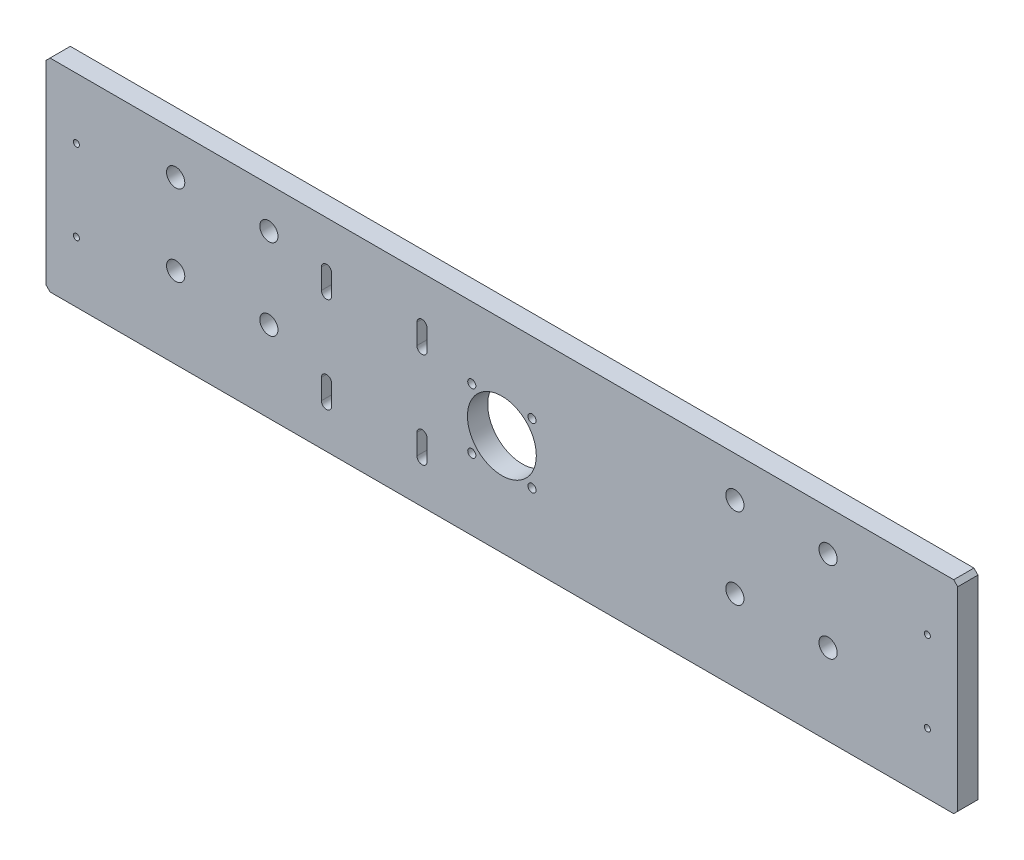
SolidWorks part; units mm, degrees
ref_plane "Piano frontale" through (0, 0, 0) normal (0, 0, 1) x (1, 0, 0)
ref_plane "Piano superiore" through (0, 0, 0) normal (0, 1, 0) x (1, 0, 0)
ref_plane "Piano destro" through (0, 0, 0) normal (1, 0, 0) x (0, 0, -1)
sketch "Schizzo1" plane through (0, 0, 0) normal (0, 0, 1) x (1, 0, 0)
  line L0 (225, 100) -> (225, 0) construction
  line L1 (2, 0) -> (448, 0)
  line L2 (0, 2) -> (0, 98)
  line L3 (2, 100) -> (448, 100)
  line L4 (450, 2) -> (450, 98)
  line L5 (87, 100) -> (87, 0) construction
  line L7 (225, 50) -> (243.5099, 50) construction
  line L9 (225, 50) -> (205.51, 69.49) construction
  line L21 (0, 98) -> (2, 100)
  line L22 (2, 0) -> (0, 2)
  line L23 (448, 0) -> (450, 2)
  line L24 (448, 100) -> (450, 98)
  circle A0 centre (225, 50) radius 17
  circle A1 centre (225, 50) radius 21 construction
  circle A2 centre (239.8492, 64.8492) radius 2
  circle A3 centre (239.8492, 35.1508) radius 2
  circle A4 centre (210.1508, 35.1508) radius 2
  circle A5 centre (386, 40) radius 4.5
  circle A6 centre (386, 80) radius 4.5
  circle A7 centre (340, 40) radius 4.5
  circle A8 centre (340, 80) radius 4.5
  circle A9 centre (435, 70) radius 1.5
  circle A10 centre (435, 30) radius 1.5
  circle A11 centre (15, 30) radius 1.5
  circle A13 centre (210.1508, 64.8492) radius 2
  circle A18 centre (15, 70) radius 1.5
  circle A29 centre (110, 80) radius 4.5
  circle A30 centre (110, 40) radius 4.5
  circle A32 centre (64, 80) radius 4.5
  circle A33 centre (64, 40) radius 4.5
  point P0 (0, 0)
  point P1 (450, 100)
  point P2 (0, 100)
  point P3 (450, 0)
  point P9 (210.1508, 64.8492)
  point P13 (210.1508, 64.8492)
  dimension "D4" = 34
  dimension "D10" = 23
  dimension "D15" = 3
  dimension "D17" = 4
  dimension "D8" = 45
  dimension "D5" = 42
  dimension "D9" = 64
  dimension "D11" = 9
  dimension "D1" = 100
  dimension "D2" = 450
  dimension "D6" = 20
  dimension "D7" = 40
  dimension "D14" = 30
  dimension "D16" = 15
extrude "Boss-Extrude1" add sketch "Schizzo1" against normal blind 10
sketch "Sketch1" plane through (0, 0, -10) normal (0, 0, -1) x (-1, 0, 0)
  line L0 (-185.5771, 72.6242) -> (-185.5771, 25.4842) construction
  line L1 (-138.4371, 72.6242) -> (-138.4371, 25.4842) construction
  line L2 (-185.5771, 67.6242) -> (-185.5771, 77.6242) construction
  line L3 (-188.0771, 67.6242) -> (-188.0771, 77.6242)
  line L4 (-183.0771, 67.6242) -> (-183.0771, 77.6242)
  line L5 (-185.5771, 49.0542) -> (-138.4371, 49.0542) construction
  line L6 (-162.0071, 49.0542) -> (-162.0071, 85.2274) construction
  line L7 (-138.4371, 67.6242) -> (-138.4371, 77.6242) construction
  line L8 (-140.9371, 67.6242) -> (-140.9371, 77.6242)
  line L9 (-135.9371, 67.6242) -> (-135.9371, 77.6242)
  line L10 (-185.5771, 20.4842) -> (-185.5771, 30.4842) construction
  line L11 (-188.0771, 20.4842) -> (-188.0771, 30.4842)
  line L12 (-183.0771, 20.4842) -> (-183.0771, 30.4842)
  line L13 (-138.4371, 20.4842) -> (-138.4371, 30.4842) construction
  line L14 (-140.9371, 20.4842) -> (-140.9371, 30.4842)
  line L15 (-135.9371, 20.4842) -> (-135.9371, 30.4842)
  arc A0 (-188.0771, 67.6242) -> (-183.0771, 67.6242) centre (-185.5771, 67.6242) ccw
  arc A1 (-183.0771, 77.6242) -> (-188.0771, 77.6242) centre (-185.5771, 77.6242) ccw
  arc A2 (-140.9371, 67.6242) -> (-135.9371, 67.6242) centre (-138.4371, 67.6242) ccw
  arc A3 (-135.9371, 77.6242) -> (-140.9371, 77.6242) centre (-138.4371, 77.6242) ccw
  arc A4 (-188.0771, 20.4842) -> (-183.0771, 20.4842) centre (-185.5771, 20.4842) ccw
  arc A5 (-183.0771, 30.4842) -> (-188.0771, 30.4842) centre (-185.5771, 30.4842) ccw
  arc A6 (-140.9371, 20.4842) -> (-135.9371, 20.4842) centre (-138.4371, 20.4842) ccw
  arc A7 (-135.9371, 30.4842) -> (-140.9371, 30.4842) centre (-138.4371, 30.4842) ccw
  point P10 (-185.5771, 72.6242)
  point P22 (-138.4371, 72.6242)
  point P28 (-185.5771, 25.4842)
  point P35 (-138.4371, 25.4842)
  dimension "D1" = 10
  dimension "D2" = 5
  dimension "D3" = 5
  dimension "D4" = 5
  dimension "D5" = 5
extrude "Cut-Extrude1" cut sketch "Sketch1" against normal through all
